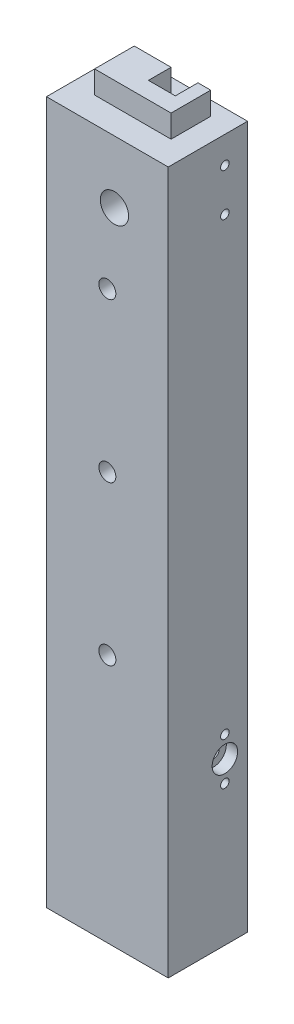
SolidWorks part; units mm, degrees
ref_plane "Front Plane" through (0, 0, 0) normal (0, 0, 1) x (1, 0, 0)
ref_plane "Top Plane" through (0, 0, 0) normal (0, 1, 0) x (1, 0, 0)
ref_plane "Right Plane" through (0, 0, 0) normal (1, 0, 0) x (0, 0, -1)
sketch "Sketch1" plane through (0, 0, 0) normal (0, 0, 1) x (1, 0, 0)
  line L1 (68.2625, 393.7) -> (-68.2625, 393.7)
  line L2 (68.2625, 393.7) -> (68.2625, -393.7)
  line L3 (68.2625, -393.7) -> (-68.2625, -393.7)
  line L4 (-68.2625, 393.7) -> (-68.2625, -393.7)
  line L5 (68.2625, 393.7) -> (-68.2625, -393.7) construction
  line L6 (68.2625, -393.7) -> (-68.2625, 393.7) construction
  point P0 (0, 0)
  dimension "D1" = 787.4
  dimension "D2" = 136.525
extrude "Boss-Extrude1" add sketch "Sketch1" along normal blind 88.9
sketch "Sketch2" plane through (0, 393.7, 0) normal (0, 1, 0) x (1, 0, 0)
  line L0 (-42.8625, -60.325) -> (42.8625, -60.325)
  line L1 (42.8625, -60.325) -> (42.8625, -15.875)
  line L2 (42.8625, -15.875) -> (28.575, -15.875)
  line L3 (28.575, -15.875) -> (28.575, -41.275)
  line L4 (28.575, -41.275) -> (-1.5875, -41.275)
  line L5 (-1.5875, -41.275) -> (-1.5875, -15.875)
  line L6 (-1.5875, -15.875) -> (-42.8625, -15.875)
  line L7 (-42.8625, -15.875) -> (-42.8625, -60.325)
  line L9 (-68.2625, -88.9) -> (-68.2625, 0) construction
  line L10 (68.2625, -88.9) -> (-68.2625, -88.9) construction
  dimension "D1" = 41.275
  dimension "D2" = 30.1625
  dimension "D3" = 25.4
  dimension "D4" = 19.05
  dimension "D5" = 28.575
  dimension "D6" = 25.4
  dimension "D7" = 85.725
extrude "Boss-Extrude2" add sketch "Sketch2" along normal blind 25.4
sketch "Sketch3" plane through (0, 0, 88.9) normal (0, 0, 1) x (1, 0, 0)
  line L0 (0, 0) -> (0, 50000) construction
  line L1 (-68.2625, -393.7) -> (68.2625, -393.7) construction
  line L2 (68.2625, -393.7) -> (68.2625, 393.7) construction
  circle A0 centre (0, 63.5) radius 9.525
  circle A1 centre (0, -114.3) radius 9.525
  circle A2 centre (0, 241.3) radius 9.525
  circle A3 centre (7.9375, 323.85) radius 15.875
  dimension "D1" = 177.8
  dimension "D2" = 177.8
  dimension "D3" = 279.4
  dimension "D4" = 19.05
  dimension "D8" = 31.75
  dimension "D5" = 68.2625
  dimension "D6" = 82.55
  dimension "D7" = 60.325
extrude "Cut-Extrude1" cut sketch "Sketch3" against normal through all
sketch "Sketch5" plane through (-68.2625, 0, 0) normal (-1, 0, 0) x (0, 0, 1)
  line L0 (88.9, -393.7) -> (0, -393.7) construction
  line L1 (60.325, -174.625) -> (15.875, -174.625)
  line L2 (60.325, -174.625) -> (60.325, -250.825)
  line L3 (60.325, -250.825) -> (15.875, -250.825)
  line L4 (15.875, -174.625) -> (15.875, -250.825)
  line L5 (60.325, -174.625) -> (15.875, -250.825) construction
  line L6 (60.325, -250.825) -> (15.875, -174.625) construction
  line L7 (0, 393.7) -> (0, -393.7) construction
  point P0 (38.1, -212.725)
  point P5 (38.1, -250.825)
  dimension "D1" = 76.2
  dimension "D2" = 44.45
  dimension "D3" = 142.875
  dimension "D4" = 15.875
extrude "Cut-Extrude2" cut sketch "Sketch5" against normal blind 19.05
sketch "Sketch6" plane through (0, 0, 0) normal (0, 0, -1) x (-1, 0, 0)
  line L0 (-68.2625, -393.7) -> (-68.2625, 393.7) construction
  line L1 (-38.1, 374.65) -> (-53.975, 374.65)
  line L2 (-38.1, 374.65) -> (-38.1, 304.8)
  line L3 (-38.1, 304.8) -> (-53.975, 304.8)
  line L4 (-53.975, 374.65) -> (-53.975, 304.8)
  line L5 (-38.1, 374.65) -> (-53.975, 304.8) construction
  line L6 (-38.1, 304.8) -> (-53.975, 374.65) construction
  line L7 (-38.1, -168.275) -> (-53.975, -168.275)
  line L8 (-38.1, -168.275) -> (-38.1, -257.175)
  line L9 (-38.1, -257.175) -> (-53.975, -257.175)
  line L10 (-53.975, -168.275) -> (-53.975, -257.175)
  line L11 (-38.1, -168.275) -> (-53.975, -257.175) construction
  line L12 (-38.1, -257.175) -> (-53.975, -168.275) construction
  line L13 (68.2625, -393.7) -> (-68.2625, -393.7) construction
  line L14 (-68.2625, 393.7) -> (68.2625, 393.7) construction
  point P0 (-46.0375, 339.725)
  point P5 (-46.0375, -212.725)
  dimension "D1" = 14.2875
  dimension "D2" = 15.875
  dimension "D3" = 136.525
  dimension "D4" = 88.9
  dimension "D5" = 69.85
  dimension "D6" = 19.05
extrude "Cut-Extrude3" cut sketch "Sketch6" against normal blind 50.8
sketch "Sketch7" plane through (68.2625, 0, 0) normal (1, 0, 0) x (0, 0, -1)
  line L0 (-15.875, -174.625) -> (-15.875, -250.825) construction
  line L1 (-15.875, -250.825) -> (-60.325, -250.825) construction
  line L2 (-60.325, -250.825) -> (-60.325, -174.625) construction
  line L3 (-60.325, -174.625) -> (-15.875, -174.625) construction
  line L4 (0, -168.275) -> (0, -257.175) construction
  line L5 (0, -257.175) -> (-50.8, -257.175) construction
  line L6 (-50.8, -257.175) -> (-50.8, -168.275) construction
  line L7 (-50.8, -168.275) -> (0, -168.275) construction
  line L8 (0, 374.65) -> (0, 304.8) construction
  line L9 (0, 304.8) -> (-50.8, 304.8) construction
  line L10 (-50.8, 304.8) -> (-50.8, 374.65) construction
  line L11 (-50.8, 374.65) -> (0, 374.65) construction
  line L12 (-15.875, -174.625) -> (-15.875, -250.825)
  line L13 (-15.875, -250.825) -> (-60.325, -250.825)
  line L14 (-60.325, -250.825) -> (-60.325, -174.625)
  line L15 (-60.325, -174.625) -> (-15.875, -174.625)
  line L16 (0, -168.275) -> (0, -257.175)
  line L17 (0, -257.175) -> (-50.8, -257.175)
  line L18 (-50.8, -257.175) -> (-50.8, -168.275)
  line L19 (-50.8, -168.275) -> (0, -168.275)
  line L20 (0, 374.65) -> (0, 304.8)
  line L21 (0, 304.8) -> (-50.8, 304.8)
  line L22 (-50.8, 304.8) -> (-50.8, 374.65)
  line L23 (-50.8, 374.65) -> (0, 374.65)
  line L24 (-50.8, 374.65) -> (0, 304.8) construction
  line L25 (-50.8, -168.275) -> (0, -257.175) construction
  line L26 (-25.4, -168.275) -> (-25.4, -257.175) construction
  line L27 (-25.4, 374.65) -> (-25.4, 304.8) construction
  line L28 (-60.325, -212.725) -> (-15.875, -212.725) construction
  circle A0 centre (-25.4, -188.9125) radius 4.7625
  circle A1 centre (-25.4, -236.5375) radius 4.7625
  circle A2 centre (-25.4, 363.5375) radius 4.7625
  circle A3 centre (-25.4, 315.9125) radius 4.7625
  circle A4 centre (-25.4, -212.725) radius 6.35
  point P16 (-25.4, -212.725)
  point P25 (-25.4, 339.725)
  point P30 (-42.1256, -212.725)
  dimension "D3" = 9.525
  dimension "D4" = 25.4
  dimension "D5" = 9.525
  dimension "D9" = 12.7
  dimension "D1" = 23.8125
  dimension "D2" = 23.8125
  dimension "D6" = 23.8125
  dimension "D7" = 23.8125
  dimension "D8" = 25.4
  dimension "D10" = 9.525
extrude "Cut-Extrude4" cut sketch "Sketch7" against normal blind 44.45 contours A1 | A0 | A3 | A2 region at (68.2625, -188.9125, 25.4) region at (68.2625, -236.5375, 25.4)
extrude "Cut-Extrude5" cut sketch "Sketch7<3>" against normal through all contours A4
sketch "Sketch7<3>" plane through (68.2625, 0, 0) normal (1, 0, 0) x (0, 0, -1) same geometry as "Sketch7"
sketch "Sketch8" plane through (68.2625, 0, 0) normal (1, 0, 0) x (0, 0, -1)
  circle A0 centre (-25.4, -212.725) radius 14.2875
  dimension "D1" = 28.575
extrude "Cut-Extrude6" cut sketch "Sketch8" against normal blind 12.7
